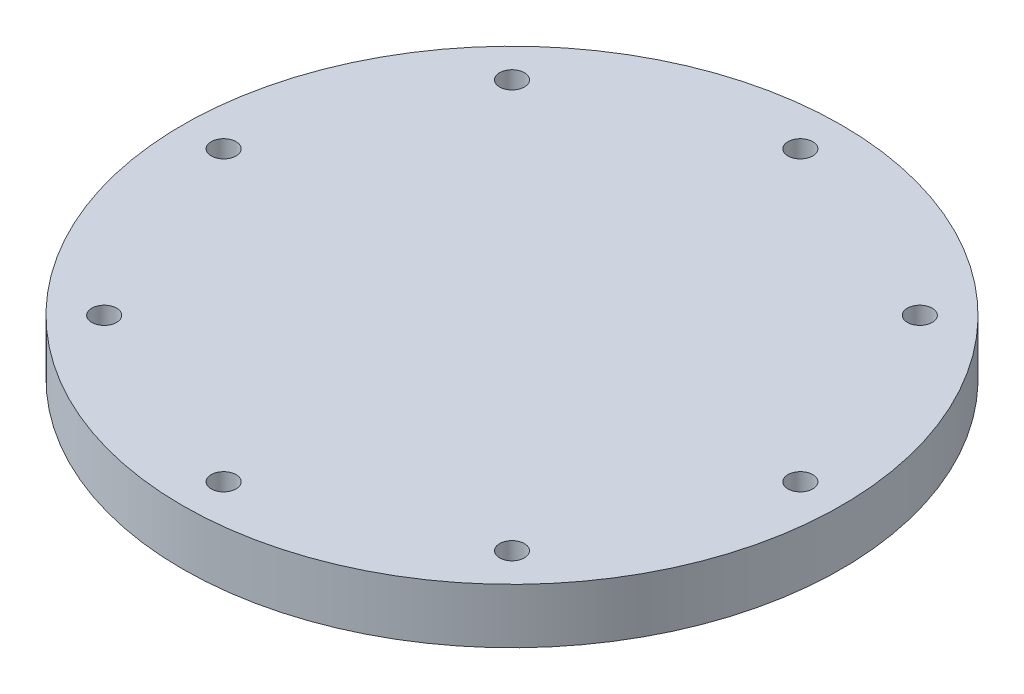
SolidWorks part; units mm, degrees
ref_plane "Front Plane" through (0, 0, 0) normal (0, 0, 1) x (1, 0, 0)
ref_plane "Top Plane" through (0, 0, 0) normal (0, 1, 0) x (1, 0, 0)
ref_plane "Right Plane" through (0, 0, 0) normal (1, 0, 0) x (0, 0, -1)
sketch "Sketch1" plane through (0, 0, 0) normal (0, 1, 0) x (1, 0, 0)
  circle A0 centre (0, 0) radius 38.1
  dimension "D1" = 76.2
extrude "Boss-Extrude1" add sketch "Sketch1" along normal blind 6.35
sketch "Sketch2" plane through (0, 0, 0) normal (0, -1, 0) x (1, 0, 0)
  circle A0 centre (0, 0) radius 33.3375
  circle A1 centre (0, 33.3375) radius 0.762
  dimension "D1" = 66.675
hole_wizard "CBORE for #4 Button Head Cap Screw1" positions "Sketch5" profile "Sketch4" counterbore size "#4" standard "ANSI Inch" end condition through all
sketch "Sketch5" plane through (0, 0, 0) normal (0, -1, 0) x (-1, 0, 0)
  point P0 (0, -33.3375)
sketch "Sketch4" plane through (0, 0, 33.3375) normal (1, 0, 0) x (0, 0, -1)
  line L0 (0, 0) -> (0, 6.35)
  line L1 (0, 6.35) -> (1.4351, 6.35)
  line L3 (1.4351, 6.35) -> (1.4351, 1.905)
  line L4 (1.4351, 1.905) -> (2.413, 1.905)
  line L5 (2.413, 1.905) -> (2.413, 0)
  line L7 (2.413, 0) -> (0, 0)
  line L11 (0, -6.35) -> (0, 107.95) construction
  dimension "Thru Hole Dia." = 2.8702
  dimension "Thru Hole Depth" = 6.35
  dimension "C'Bore Dia." = 4.826
  dimension "C'Bore Depth" = 1.905
pattern_circular "CirPattern1" count 8 over 360 about axis through (0, 0, 0) along (0, 1, 0) of "CBORE for #4 Button Head Cap Screw1"
